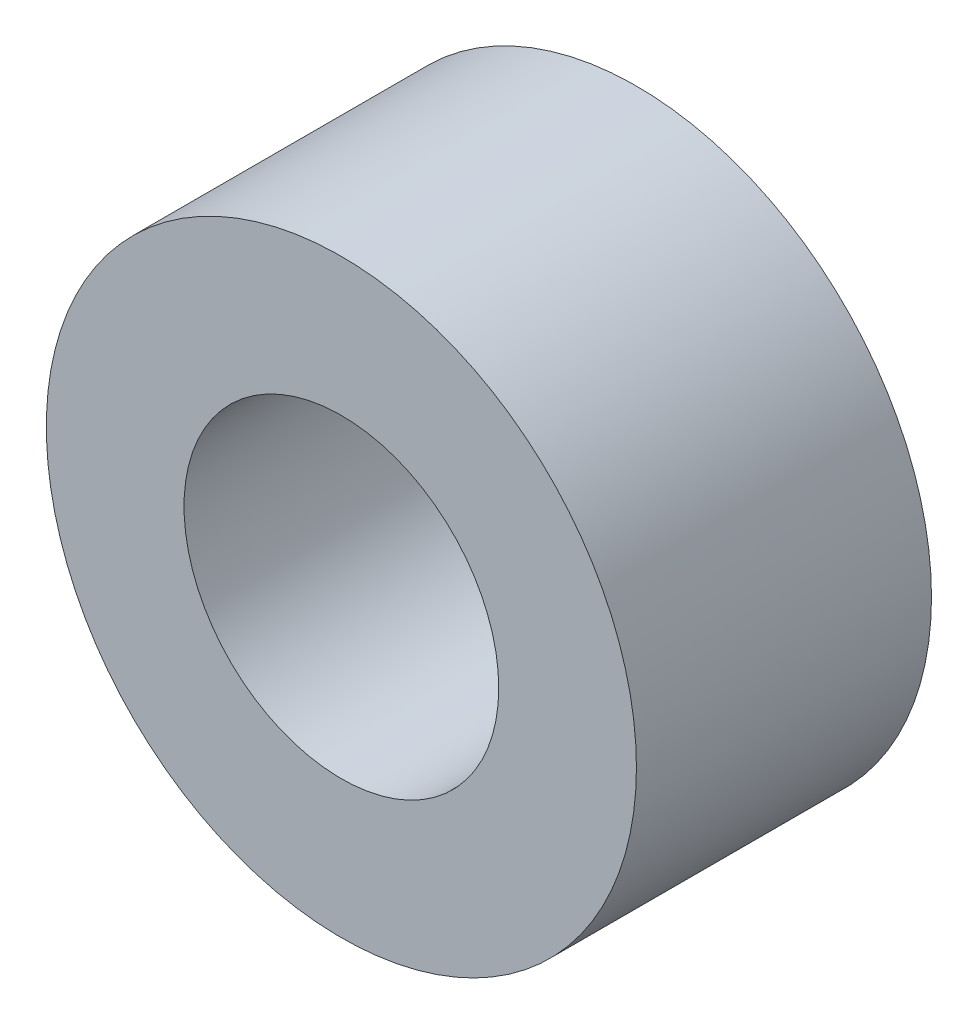
SolidWorks part; units mm, degrees
ref_plane "Front Plane" through (0, 0, 0) normal (0, 0, 1) x (1, 0, 0)
ref_plane "Top Plane" through (0, 0, 0) normal (0, 1, 0) x (1, 0, 0)
ref_plane "Right Plane" through (0, 0, 0) normal (1, 0, 0) x (0, 0, -1)
sketch "Sketch1" plane through (0, 0, 0) normal (0, 0, 1) x (1, 0, 0)
  circle A0 centre (0, 0) radius 3
  circle A1 centre (0, 0) radius 1.6
  dimension "OD" = 6
  dimension "ID" = 3.2
extrude "Extrude1" add sketch "Sketch1" along normal mid plane 3
sketch "Sketch2" plane through (0, 0, 0) normal (1, 0, 0) x (0, 0, -1)
  line L0 (-1.5, -1.6) -> (1.5, -1.6) construction
  line L3 (1.5, 1.6) -> (-1.5, 1.6) construction
  line L5 (-1.5, -1.6) -> (1.5, -1.6)
  line L6 (1.5, 1.6) -> (-1.5, 1.6)
sketch "Sketch4" plane through (0, 0, 1.5) normal (0, 0, 1) x (1, 0, 0)
  line L0 (0, 0) -> (-1.1314, 1.1314)
  line L1 (0, -1.1) -> (0, 1.1) construction
  circle A0 centre (0, 0) radius 1.6 construction
  dimension "D1" = 45
